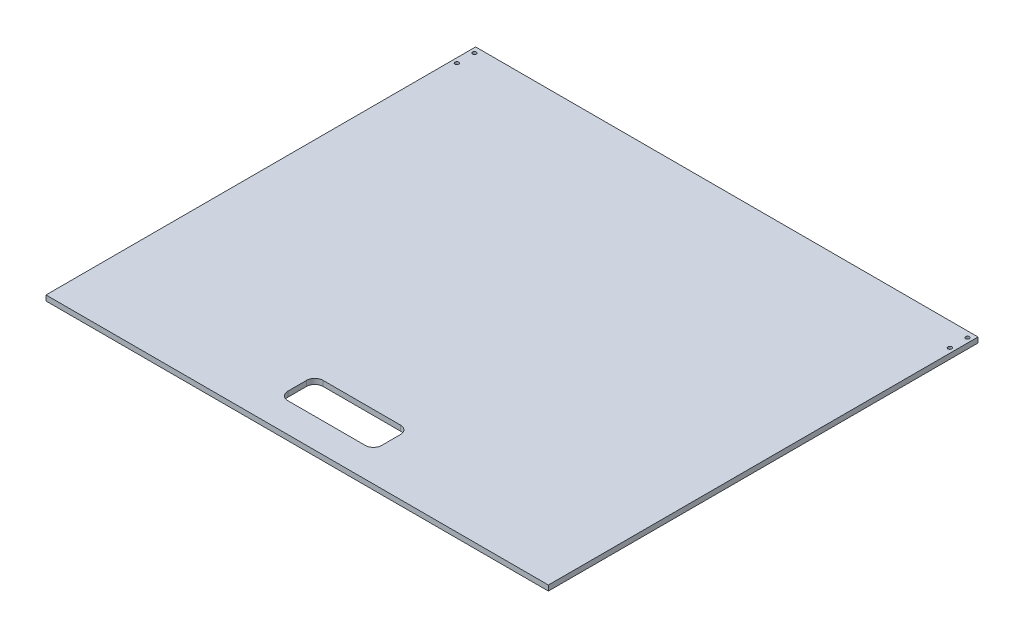
SolidWorks part; units mm, degrees
ref_plane "Front Plane" through (0, 0, 0) normal (0, 0, 1) x (1, 0, 0)
ref_plane "Top Plane" through (0, 0, 0) normal (0, 1, 0) x (1, 0, 0)
ref_plane "Right Plane" through (0, 0, 0) normal (1, 0, 0) x (0, 0, -1)
sketch "Sketch1" plane through (0, 0, 0) normal (0, 1, 0) x (1, 0, 0)
  line L1 (-214, -183) -> (214, -183)
  line L2 (-214, -183) -> (-214, 183)
  line L3 (-214, 183) -> (214, 183)
  line L4 (214, -183) -> (214, 183)
  line L5 (-214, -183) -> (214, 183) construction
  line L6 (-214, 183) -> (214, -183) construction
  point P0 (0, 0)
  dimension "D1" = 428
  dimension "D2" = 366
extrude "Boss-Extrude1" add sketch "Sketch1" along normal blind 4.5
sketch "Sketch2" plane through (0, 0, 0) normal (0, -1, 0) x (1, 0, 0)
  line L0 (214, -183) -> (-214, -183) construction
  line L1 (214, 183) -> (214, -183) construction
  circle A0 centre (210, -163) radius 1.6
  circle A1 centre (210, -178) radius 1.6
  dimension "D1" = 5
  dimension "D3" = 3.2
  dimension "D2" = 15
  dimension "D4" = 4
extrude "Cut-Extrude1" cut sketch "Sketch2" against normal through all
mirror "Mirror1" about plane through (0, 0, 0) normal (1, 0, 0) of "Cut-Extrude1"
sketch "Sketch3" plane through (0, 4.5, 0) normal (0, 1, 0) x (1, 0, 0)
  line L0 (-214, -183) -> (214, -183) construction
  line L1 (-33, -158) -> (33, -158)
  line L2 (-40, -151) -> (-40, -135)
  line L3 (-33, -128) -> (33, -128)
  line L4 (40, -151) -> (40, -135)
  line L5 (-40, -158) -> (40, -128) construction
  line L6 (-40, -128) -> (40, -158) construction
  arc A0 (-40, -135) -> (-33, -128) centre (-33, -135) cw
  arc A1 (-33, -158) -> (-40, -151) centre (-33, -151) cw
  arc A2 (33, -158) -> (40, -151) centre (33, -151) ccw
  arc A3 (33, -128) -> (40, -135) centre (33, -135) cw
  point P0 (0, -143)
  dimension "D4" = 7
  dimension "D1" = 25
  dimension "D2" = 80
  dimension "D3" = 30
extrude "Cut-Extrude2" cut sketch "Sketch3" against normal through all
